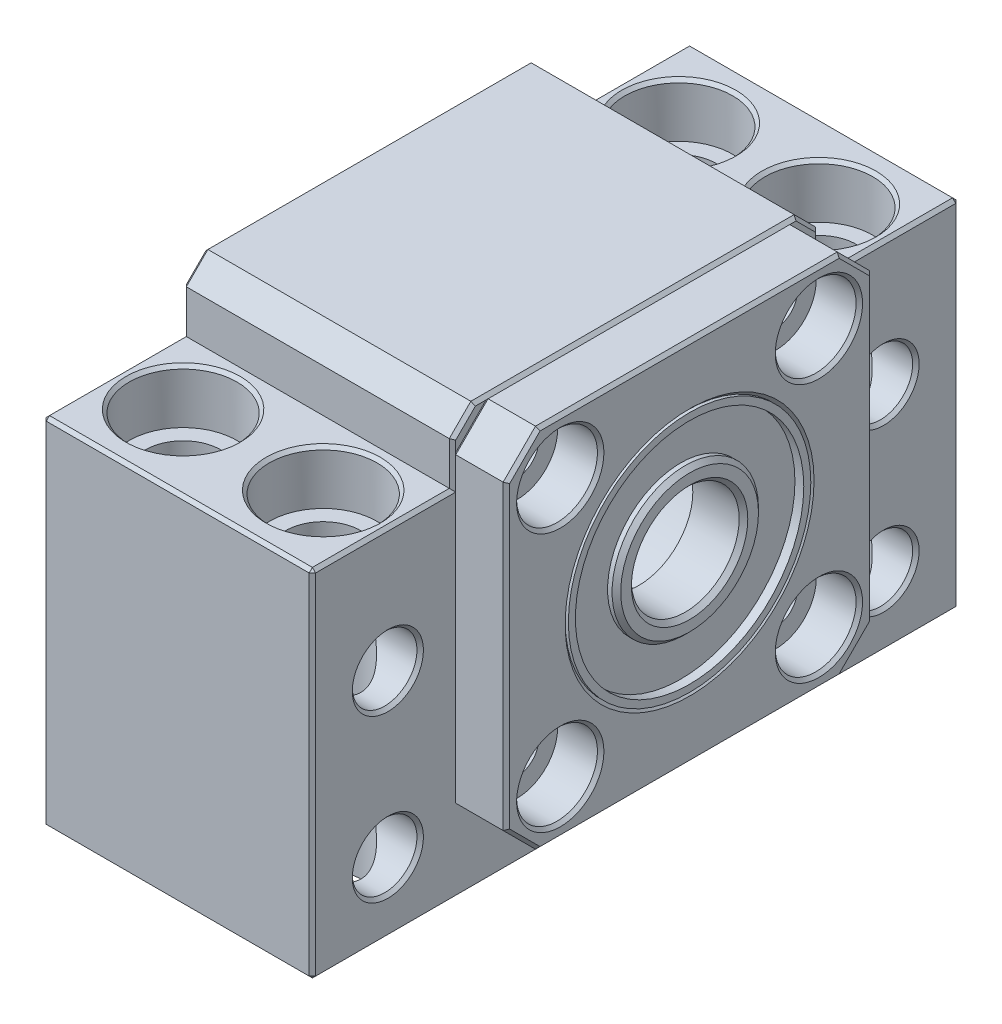
SolidWorks part; units mm, degrees
material "1060 Alloy"
ref_plane "Front Plane" through (0, 0, 0) normal (0, 0, 1) x (1, 0, 0)
ref_plane "Top Plane" through (0, 0, 0) normal (0, 1, 0) x (1, 0, 0)
ref_plane "Right Plane" through (0, 0, 0) normal (1, 0, 0) x (0, 0, -1)
sketch "Sketch1" plane through (0, 0, 0) normal (1, 0, 0) x (0, 0, -1)
  line L0 (0, 33.6136) -> (0, 0) construction
  line L1 (17, 17) -> (-17, 17)
  line L2 (-17, 17) -> (-17, 11)
  line L3 (-17, 11) -> (-30, 11)
  line L4 (-30, 11) -> (-30, -22)
  line L5 (-30, -22) -> (30, -22)
  line L6 (-17, 17) -> (-17, -17) construction
  line L7 (-17, -17) -> (0, -17) construction
  line L8 (30, 11) -> (30, -22)
  line L9 (17, 11) -> (30, 11)
  line L10 (17, 17) -> (17, 11)
  line L11 (17, 17) -> (17, -17) construction
  line L12 (17, -17) -> (0, -17) construction
  line L13 (-17, 17) -> (17, -17) construction
  point P1 (0, 0)
  point P12 (0, -22)
  point P15 (0, 17)
  dimension "D1" = 17
  dimension "D2" = 33
  dimension "D3" = 30
  dimension "D4" = 6
extrude "Boss-Extrude1" add sketch "Sketch1" along normal mid plane 25
sketch "Sketch2" plane through (12.5, 0, 0) normal (1, 0, 0) x (0, 0, -1)
  line L0 (17, 11) -> (17, 17) construction
  line L1 (17, -17) -> (-17, -17)
  line L2 (17, -17) -> (17, 17)
  line L3 (17, 17) -> (-17, 17)
  line L4 (-17, -17) -> (-17, 17)
  line L5 (17, -17) -> (-17, 17) construction
  line L6 (17, 17) -> (-17, -17) construction
  point P0 (0, 0)
extrude "Boss-Extrude2" add sketch "Sketch2" along normal blind 5
sketch "Sketch4" plane through (17.5, 0, 0) normal (1, 0, 0) x (0, 0, -1)
  line L0 (-23, -0.5) -> (-23, -15.5) construction
  line L1 (12, -12) -> (-12, -12) construction
  line L2 (12, -12) -> (12, 12) construction
  line L3 (12, 12) -> (-12, 12) construction
  line L4 (-12, -12) -> (-12, 12) construction
  line L5 (12, -12) -> (-12, 12) construction
  line L6 (12, 12) -> (-12, -12) construction
  line L7 (-30, -22) -> (30, -22) construction
  line L8 (-30, 11) -> (-30, -22) construction
  line L9 (0, 35.0853) -> (0, 17.5761) construction
  circle A0 centre (0, 0) radius 11.25
  circle A1 centre (-12, 12) radius 2
  circle A2 centre (12, 12) radius 2
  circle A3 centre (12, -12) radius 2
  circle A4 centre (-12, -12) radius 2
  circle A5 centre (-23, -0.5) radius 3
  circle A6 centre (-23, -15.5) radius 3
  circle A7 centre (23, -15.5) radius 3
  circle A8 centre (23, -0.5) radius 3
  dimension "D1" = 22.5
  dimension "D2" = 4
  dimension "D5" = 6
  dimension "D3" = 24
  dimension "D4" = 15
  dimension "D6" = 6.5
  dimension "D7" = 7
extrude "Cut-Extrude1" cut sketch "Sketch4" against normal through all
sketch "Sketch5" plane through (17.5, 0, 0) normal (1, 0, 0) x (0, 0, -1)
  circle A0 centre (-12, 12) radius 3.75
  circle A1 centre (12, 12) radius 3.75
  circle A2 centre (12, -12) radius 3.75
  circle A3 centre (-12, -12) radius 3.75
  dimension "D1" = 7.5
extrude "Cut-Extrude2" cut sketch "Sketch5" against normal blind 4
sketch "Sketch6" plane through (0, 11, 0) normal (0, 1, 0) x (1, 0, 0)
  line L1 (6.5, 23) -> (-6.5, 23) construction
  line L2 (6.5, 23) -> (6.5, -23) construction
  line L3 (6.5, -23) -> (-6.5, -23) construction
  line L4 (-6.5, 23) -> (-6.5, -23) construction
  line L5 (6.5, 23) -> (-6.5, -23) construction
  line L6 (6.5, -23) -> (-6.5, 23) construction
  circle A0 centre (-6.5, 23) radius 3.5
  circle A1 centre (6.5, 23) radius 3.5
  circle A2 centre (-6.5, -23) radius 3.5
  circle A3 centre (6.5, -23) radius 3.5
  point P0 (0, 0)
  dimension "D3" = 7
  dimension "D1" = 46
  dimension "D2" = 13
extrude "Cut-Extrude3" cut sketch "Sketch6" against normal through all
sketch "Sketch7" plane through (0, 11, 0) normal (0, 1, 0) x (1, 0, 0)
  circle A0 centre (-6.5, 23) radius 5
  circle A1 centre (6.5, 23) radius 5
  circle A2 centre (6.5, -23) radius 5
  circle A3 centre (-6.5, -23) radius 5
  dimension "D1" = 10
extrude "Cut-Extrude4" cut sketch "Sketch7" against normal blind 5
ref_plane "Plane1" through (12.5, 0, 0) normal (1, 0, 0) x (0, 0, -1)
split "Split1" trim tools "Plane1" bodies to split 106 resulting bodies 107 108
chamfer "Chamfer1" distance 2 distance2 2 2 edges at (0, 17, -17) (0, 17, 17)
chamfer "Chamfer2" distance 3 distance2 3 4 edges at (15, -17, -17) (15, -17, 17) (15, 17, -17) (15, 17, 17)
chamfer "Chamfer3" distance 0.3 angle 45 26 edges at (17.5, -15.5, 15.5) (17.5, 0, 17) (17.5, 15.5, 15.5) (17.5, 17, 0) (17.5, 15.5, -15.5) (17.5, 0, -17) (17.5, -15.5, -15.5) (17.5, -17, 0) (12.5, 17, 0) (17.5, 0, -11.25) (17.5, 12, 8.25) (17.5, -12, 8.25) (17.5, -12, -15.75) (17.5, 12, -15.75) (12.5, 12, -14) (12.5, -12, 10) (12.5, 15.5, -15.5) (12.5, 15.5, 15.5) (12.5, 0, 17) (12.5, -15.5, 15.5) (12.5, -17, 0) (12.5, -15.5, -15.5) (12.5, 0, -17) (12.5, 0, -11.25) (12.5, 12, 10) (12.5, -12, -14)
chamfer "Chamfer4" distance 0.3 angle 45 46 edges at (-12.5, 0, -11.25) (-12.5, 12, 10) (-12.5, 12, -14) (-12.5, -12, -14) (-12.5, -12, 10) (-12.5, -0.5, 20) (-12.5, -15.5, 20) (-12.5, -15.5, -20) (-12.5, -0.5, -20) (12.5, -0.5, 26) (12.5, -15.5, 26) (12.5, -15.5, -20) (12.5, -0.5, -20) (12.5, -12, -14) (12.5, 12, 10) (12.5, 0, -11.25) (0, -22, -30) (0, 11, -30) (0, 11, 30) (-12.5, 16, 16) (-12.5, 13, 17) (-12.5, 11, 23.5) (-12.5, -5.5, 30) (-12.5, 17, 0) (-12.5, 16, -16) (-12.5, 13, -17) (-12.5, 11, -23.5) (-12.5, -5.5, -30) (-12.5, -22, 0) (0, -22, 30) (12.5, 11, -23.5) (12.5, -5.5, -30) (12.5, -22, 0) (12.5, -5.5, 30) (12.5, 11, 23.5) (12.5, 13, 17) (12.5, 16, 16) (12.5, 17, 0) (12.5, 16, -16) (12.5, 13, -17) (12.5, -12, 10) (12.5, 12, -14) (6.5, 11, -18) (-6.5, 11, -18) (-6.5, 11, 28) (6.5, 11, 28)
ref_axis "Axis1" through (-14, 0, 0) along (1, 0, 0)
sketch "Sketch8" plane through (0, 0, 0) normal (0, 1, 0) x (1, 0, 0)
  line L0 (17.5, 13.8757) -> (17.5, -13.8757) construction
  line L1 (12.8, 11.25) -> (17.5, 11.25)
  line L2 (12.8, 11.25) -> (12.8, 5)
  line L3 (12.8, 5) -> (17.5, 5)
  line L4 (17.5, 11.25) -> (17.5, 10.5969)
  line L5 (18.9331, 0) -> (9.2061, 0) construction
  line L7 (17.5, 6.7929) -> (17.5, 5)
  line L8 (17.5, 10.5969) -> (16.6809, 10.5969)
  line L10 (17.5, 6.7929) -> (16.6809, 6.7929)
  line L11 (16.6809, 10.5969) -> (16.6809, 6.7929)
  dimension "D1" = 5
revolve "Revolve1" add sketch "Sketch8" angle 360 about L5
chamfer "Chamfer5" distance 0.4 angle 45 2 edges at (17.5, 0, -5) (17.5, 0, -6.7929)
ref_plane "Plane2" through (2.5, 0, 0) normal (1, 0, 0) x (0, 0, -1)
mirror "Mirror1" about plane through (2.5, 0, 0) normal (1, 0, 0) of bodies 109
